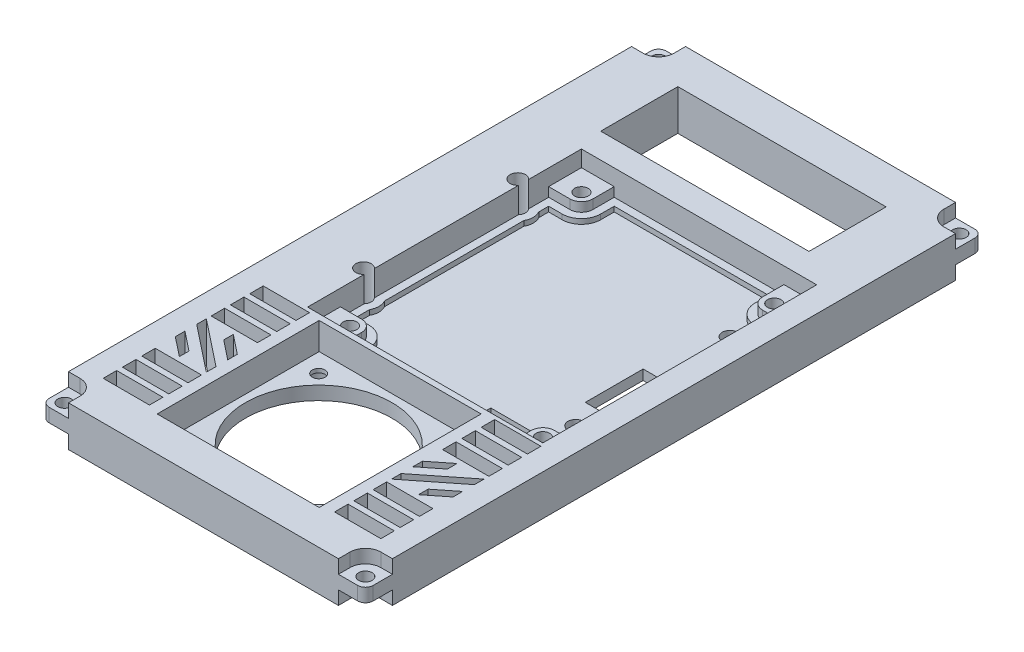
SolidWorks part; units mm, degrees
ref_plane "前视基准面" through (0, 0, 0) normal (0, 0, 1) x (1, 0, 0)
ref_plane "上视基准面" through (0, 0, 0) normal (0, 1, 0) x (1, 0, 0)
ref_plane "右视基准面" through (0, 0, 0) normal (1, 0, 0) x (0, 0, -1)
sketch "草图1" plane through (0, 0, 0) normal (0, 1, 0) x (1, 0, 0)
  line L1 (0, 0) -> (84, 0)
  line L2 (0, 0) -> (0, 160)
  line L3 (0, 160) -> (84, 160)
  line L4 (84, 0) -> (84, 160)
  dimension "D1" = 84
  dimension "D2" = 160
extrude "凸台-拉伸1" add sketch "草图1" along normal blind 10.5
fillet "圆角1" radius 2 4 edges at (0, 5.25, 0) (0, 5.25, -160) (84, 5.25, -160) (84, 5.25, 0)
sketch "草图2" plane through (0, 10.5, 0) normal (0, 1, 0) x (1, 0, 0)
  line L0 (0, 158) -> (0, 2) construction
  line L1 (2, 0) -> (82, 0) construction
  line L2 (42, 160) -> (42, 0) construction
  line L3 (82, 160) -> (2, 160) construction
  line L20 (73, 27.25) -> (78, 31.2083)
  line L21 (73, 24.75) -> (73, 27.25)
  line L22 (78, 28.7083) -> (73, 24.75)
  line L23 (78, 31.2083) -> (78, 28.7083)
  line L36 (66, 24.75) -> (66, 27.25)
  line L38 (6, 28.7083) -> (11, 24.75)
  line L40 (78, 34.25) -> (66, 24.75)
  line L42 (6, 36.75) -> (18, 36.75) construction
  line L43 (6, 36.75) -> (6, 24.75) construction
  line L44 (6, 24.75) -> (18, 24.75) construction
  line L45 (18, 36.75) -> (18, 24.75) construction
  line L46 (6, 36.75) -> (18, 24.75) construction
  line L47 (6, 24.75) -> (18, 36.75) construction
  line L48 (11, 24.75) -> (11, 27.25)
  line L49 (11, 27.25) -> (6, 31.2083)
  line L50 (6, 31.2083) -> (6, 28.7083)
  line L55 (6, 36.75) -> (6, 34.25)
  line L56 (6, 34.25) -> (18, 24.75)
  line L57 (18, 24.75) -> (18, 27.25)
  line L58 (18, 27.25) -> (6, 36.75)
  line L59 (13, 36.75) -> (13, 34.25)
  line L60 (13, 34.25) -> (18, 30.2917)
  line L61 (18, 30.2917) -> (18, 32.7917)
  line L62 (18, 32.7917) -> (13, 36.75)
  line L63 (78, 36.75) -> (78, 34.25)
  line L64 (66, 27.25) -> (78, 36.75)
  line L65 (66, 30.2917) -> (66, 32.7917)
  line L66 (71, 34.25) -> (66, 30.2917)
  line L67 (71, 36.75) -> (71, 34.25)
  line L68 (66, 32.7917) -> (71, 36.75)
  line L69 (6, 41.5) -> (6, 38)
  line L70 (6, 13.5) -> (18, 13.5)
  line L71 (6, 13.5) -> (6, 10)
  line L72 (6, 10) -> (18, 10)
  line L73 (18, 13.5) -> (18, 10)
  line L74 (6, 41.5) -> (18, 41.5)
  line L75 (18, 41.5) -> (18, 38)
  line L76 (6, 38) -> (18, 38)
  line L77 (6, 18.5) -> (6, 15)
  line L78 (6, 18.5) -> (18, 18.5)
  line L79 (18, 18.5) -> (18, 15)
  line L80 (6, 15) -> (18, 15)
  line L81 (6, 46.5) -> (6, 43)
  line L82 (6, 43) -> (18, 43)
  line L83 (18, 46.5) -> (18, 43)
  line L84 (6, 46.5) -> (18, 46.5)
  line L85 (6, 23.5) -> (6, 20)
  line L86 (6, 23.5) -> (18, 23.5)
  line L87 (18, 23.5) -> (18, 20)
  line L88 (6, 20) -> (18, 20)
  line L89 (6, 51.5) -> (6, 48)
  line L90 (6, 48) -> (18, 48)
  line L91 (18, 51.5) -> (18, 48)
  line L92 (6, 51.5) -> (18, 51.5)
  line L93 (78, 10) -> (66, 10)
  line L94 (66, 13.5) -> (66, 10)
  line L95 (78, 13.5) -> (66, 13.5)
  line L96 (78, 13.5) -> (78, 10)
  line L97 (78, 18.5) -> (66, 18.5)
  line L98 (66, 18.5) -> (66, 15)
  line L99 (78, 15) -> (66, 15)
  line L100 (78, 18.5) -> (78, 15)
  line L101 (78, 23.5) -> (66, 23.5)
  line L102 (66, 23.5) -> (66, 20)
  line L103 (78, 20) -> (66, 20)
  line L104 (78, 23.5) -> (78, 20)
  line L105 (78, 41.5) -> (66, 41.5)
  line L106 (66, 41.5) -> (66, 38)
  line L107 (78, 38) -> (66, 38)
  line L108 (78, 41.5) -> (78, 38)
  line L109 (78, 46.5) -> (66, 46.5)
  line L110 (66, 46.5) -> (66, 43)
  line L111 (78, 43) -> (66, 43)
  line L112 (78, 46.5) -> (78, 43)
  line L113 (78, 51.5) -> (66, 51.5)
  line L114 (66, 51.5) -> (66, 48)
  line L115 (78, 48) -> (66, 48)
  line L116 (78, 51.5) -> (78, 48)
  point P33 (12, 30.75)
  dimension "D1" = 6
  dimension "D4" = 24.75
  dimension "D5" = 6
  dimension "D6" = 10
  dimension "D7" = 3.5
  dimension "D8" = 12
  dimension "D9" = 2
  dimension "D10" = 3
  dimension "D25" = 12
  dimension "D26" = 12
  dimension "D27" = 2.5
  dimension "D28" = 2.5
  dimension "D29" = 2.5
  dimension "D30" = 5
  dimension "D31" = 5
extrude "切除-拉伸1" cut sketch "草图2" against normal through all
sketch "草图4" plane through (0, 10.5, 0) normal (0, 1, 0) x (1, 0, 0)
  line L0 (-0.1195, 30) -> (83.8805, 30) construction
  line L3 (41.8805, 0) -> (41.8805, 72.0189) construction
  line L5 (2, 0) -> (82, 0) construction
  line L6 (25.8805, 46) -> (57.8805, 46) construction
  line L7 (25.8805, 46) -> (25.8805, 14) construction
  line L8 (25.8805, 14) -> (57.8805, 14) construction
  line L9 (57.8805, 46) -> (57.8805, 14) construction
  circle A0 centre (41.8805, 30) radius 19
  circle A1 centre (57.8805, 14) radius 1.65
  circle A2 centre (57.8805, 46) radius 1.65
  circle A3 centre (25.8805, 46) radius 1.65
  circle A4 centre (25.8805, 14) radius 1.65
  dimension "D1" = 38
  dimension "D7" = 3.3
  dimension "D2" = 30
  dimension "D3" = 32
  dimension "D4" = 32
  dimension "D5" = 16
  dimension "D6" = 16
extrude "切除-拉伸2" cut sketch "草图4" against normal through all
sketch "草图6" plane through (0, 10.5, 0) normal (0, 1, 0) x (1, 0, 0)
  line L1 (82, 160) -> (2, 160) construction
  line L13 (66, 90) -> (76, 90)
  line L14 (66, 90) -> (66, 75)
  line L15 (66, 75) -> (76, 75)
  line L16 (76, 90) -> (76, 75)
  line L35 (55, 55) -> (67.5, 55)
  line L36 (55, 55) -> (55, 61.5)
  line L37 (55, 61.5) -> (67.5, 61.5)
  line L38 (67.5, 55) -> (67.5, 61.5)
  line L40 (84, 2) -> (84, 158) construction
  line L41 (2, 0) -> (82, 0) construction
  dimension "D2" = 70
  dimension "D3" = 8
  dimension "D4" = 16.5
  dimension "D5" = 55
  dimension "D6" = 12.5
  dimension "D7" = 6.5
  dimension "D8" = 10
  dimension "D10" = 15
extrude "切除-拉伸3" cut sketch "草图6" against normal through all
sketch "草图7" plane through (0, 10.5, 0) normal (0, 1, 0) x (1, 0, 0)
  line L0 (0, 108.5) -> (84, 108.5) construction
  line L3 (0, 68.5) -> (84, 68.5) construction
  line L4 (15, 108.5) -> (15, 68.5) construction
  line L5 (70, 108.5) -> (70, 68.5) construction
  line L7 (0, 158) -> (0, 2) construction
  line L8 (82, 160) -> (2, 160) construction
  circle A0 centre (15, 108.5) radius 2
  circle A1 centre (70, 108.5) radius 2
  circle A2 centre (15, 68.5) radius 2
  circle A3 centre (70, 68.5) radius 2
  dimension "D1" = 4
  dimension "D2" = 15
  dimension "D3" = 40
  dimension "D4" = 51.5
  dimension "D5" = 55
extrude "切除-拉伸4" cut sketch "草图7" against normal through all
sketch "草图8" plane through (0, 10.5, 0) normal (0, 1, 0) x (1, 0, 0)
  line L0 (42, 160) -> (42, 166.0083)
  line L1 (82, 160) -> (2, 160) construction
  line L4 (55, 55) -> (67.5, 55)
  line L5 (67.5, 55) -> (67.5, 61.5)
  line L6 (67.5, 61.5) -> (55, 61.5)
  line L7 (55, 61.5) -> (55, 55)
  line L25 (84, 160) -> (0, 160) construction
  line L28 (0, 160) -> (0, 0) construction
  line L31 (0, 0) -> (84, 0) construction
  line L34 (84, 0) -> (84, 160) construction
  line L176 (42, 30) -> (61, 30) construction
  line L177 (42, 30) -> (42, 11) construction
  line L179 (21, 51) -> (63, 51)
  line L180 (21, 51) -> (21, 9)
  line L181 (21, 9) -> (63, 9)
  line L182 (63, 51) -> (63, 9)
  line L189 (16.5, 123.5) -> (77.5, 123.5)
  line L190 (16.5, 123.5) -> (16.5, 52.5)
  line L191 (16.5, 52.5) -> (77.5, 52.5)
  line L192 (77.5, 123.5) -> (77.5, 52.5)
  line L194 (22, 118) -> (72, 118) construction
  line L195 (22, 118) -> (22, 58) construction
  line L196 (22, 58) -> (72, 58) construction
  line L197 (72, 118) -> (72, 58) construction
  circle A0 centre (22, 58) radius 1.75
  circle A1 centre (72, 58) radius 1.75
  circle A4 centre (72, 118) radius 1.75
  circle A5 centre (22, 118) radius 1.75
  circle A6 centre (81, 157) radius 1.75
  circle A7 centre (3, 157) radius 1.75
  circle A13 centre (22, 58) radius 3
  circle A14 centre (22, 118) radius 3
  circle A15 centre (72, 118) radius 3
  circle A16 centre (72, 58) radius 3
  circle A19 centre (81, 3) radius 1.75
  circle A20 centre (3, 3) radius 1.75
  dimension "D15" = 6
  dimension "D7" = 3.5
  dimension "D2" = 42
  dimension "D3" = 42
  dimension "D4" = 21
  dimension "D5" = 21
  dimension "D6" = 6.5
  dimension "D8" = 61
  dimension "D9" = 71
  dimension "D10" = 52.5
  dimension "D11" = 60
  dimension "D12" = 50
  dimension "D13" = 5.5
  dimension "D14" = 5.5
extrude "切除-拉伸5" cut sketch "草图8" against normal through all contours A7 | A6 | A4 | A5 | A0 | A1 | A19 | A20 region at (22, 10.5, -58) region at (72, 10.5, -58) region at (72, 10.5, -118) region at (22, 10.5, -118) region at (81, 10.5, -157) region at (3, 10.5, -157) region at (81, 10.5, -3) region at (3, 10.5, -3)
sketch "草图9" plane through (0, 10.5, 0) normal (0, 1, 0) x (1, 0, 0)
  line L8 (7, 160) -> (2, 160)
  line L9 (0, 158) -> (0, 153)
  line L10 (0, 153) -> (3, 153)
  line L11 (7, 157) -> (7, 160)
  line L16 (84, 153) -> (84, 158)
  line L17 (82, 160) -> (77, 160)
  line L18 (77, 160) -> (77, 157)
  line L19 (81, 153) -> (84, 153)
  line L24 (0, 7) -> (0, 2)
  line L25 (2, 0) -> (7, 0)
  line L26 (7, 0) -> (7, 3)
  line L27 (3, 7) -> (0, 7)
  line L32 (77, 0) -> (82, 0)
  line L33 (84, 2) -> (84, 7)
  line L34 (84, 7) -> (81, 7)
  line L35 (77, 3) -> (77, 0)
  arc A4 (2, 160) -> (0, 158) centre (2, 158) ccw
  arc A5 (3, 153) -> (7, 157) centre (3, 157) ccw
  arc A8 (84, 158) -> (82, 160) centre (82, 158) ccw
  arc A9 (77, 157) -> (81, 153) centre (81, 157) ccw
  arc A12 (0, 2) -> (2, 0) centre (2, 2) ccw
  arc A13 (7, 3) -> (3, 7) centre (3, 3) ccw
  arc A16 (82, 0) -> (84, 2) centre (82, 2) ccw
  arc A17 (81, 7) -> (77, 3) centre (81, 3) ccw
extrude "切除-拉伸6" cut sketch "草图9" against normal blind 3.5
extrude "切除-拉伸8" cut sketch "草图9<2>" along normal blind 3.5 from surface starting at face at (81, 0, -155.25)
sketch "草图9<2>" plane through (0, 10.5, 0) normal (0, 1, 0) x (1, 0, 0) same geometry as "草图9"
sketch "草图10" plane through (0, 0, 0) normal (0, -1, 0) x (-1, 0, 0)
  circle A0 centre (-71.8805, 118) radius 3.5
  circle A1 centre (-21.8805, 118) radius 3.5
  circle A2 centre (-21.8805, 58) radius 3.5
  circle A3 centre (-71.8805, 58) radius 3.5
  circle A8 centre (-57.8805, 14) radius 3
  circle A9 centre (-25.8805, 14) radius 3
  circle A10 centre (-25.8805, 46) radius 3
  circle A11 centre (-57.8805, 46) radius 3
  dimension "D1" = 7
extrude "切除-拉伸7" cut sketch "草图10" against normal blind 2.5
extrude "切除-拉伸9" cut sketch "草图8<4>" against normal blind 7 contours L182 L179 L180 L181 region at (42, 10.5, -30)
sketch "草图8<4>" plane through (0, 10.5, 0) normal (0, 1, 0) x (1, 0, 0) same geometry as "草图8"
extrude "切除-拉伸10" cut sketch "草图8<5>" against normal blind 6.5 contours L189 L192 L191 L190
sketch "草图8<5>" plane through (0, 10.5, 0) normal (0, 1, 0) x (1, 0, 0) same geometry as "草图8"
extrude "凸台-拉伸2" add sketch "草图8<6>" along normal blind 2.3 from surface contours A14 A5 | A15 A4 | A16 A1 | A13 A0 region at (19.0849, 10.5, -58) region at (19.0849, 10.5, -118) region at (69.0849, 10.5, -118) region at (69.0849, 10.5, -58) starting at face at (71, 4, -82.5)
sketch "草图8<6>" plane through (0, 10.5, 0) normal (0, 1, 0) x (1, 0, 0) same geometry as "草图8"
sketch "草图11" plane through (0, 4, 0) normal (0, 1, 0) x (1, 0, 0)
  line L0 (22, 115) -> (16.5, 115)
  line L1 (16.5, 123.5) -> (16.5, 109.8229) construction
  line L2 (16.5, 115) -> (16.5, 123.5)
  line L3 (16.5, 123.5) -> (25, 123.5)
  line L4 (16.5, 123.5) -> (77.5, 123.5) construction
  line L5 (25, 123.5) -> (25, 118)
  line L6 (72, 115) -> (77.5, 115)
  line L7 (77.5, 123.5) -> (77.5, 52.5) construction
  line L8 (77.5, 115) -> (77.5, 123.5)
  line L9 (77.5, 123.5) -> (69, 123.5)
  line L10 (16.5, 123.5) -> (77.5, 123.5) construction
  line L11 (69, 123.5) -> (69, 118)
  line L12 (72, 61) -> (77.5, 61)
  line L13 (77.5, 123.5) -> (77.5, 52.5) construction
  line L14 (77.5, 61) -> (77.5, 52.5)
  line L15 (77.5, 52.5) -> (69, 52.5)
  line L16 (16.5, 52.5) -> (77.5, 52.5) construction
  line L17 (69, 52.5) -> (69, 58)
  line L18 (22, 61) -> (16.5, 61)
  line L19 (16.5, 67.1771) -> (16.5, 52.5) construction
  line L20 (16.5, 61) -> (16.5, 52.5)
  line L21 (16.5, 52.5) -> (25, 52.5)
  line L22 (16.5, 52.5) -> (77.5, 52.5) construction
  line L23 (25, 52.5) -> (25, 58)
  circle A0 centre (22, 118) radius 3 construction
  circle A1 centre (22, 118) radius 3 construction
  circle A2 centre (72, 118) radius 3 construction
  circle A3 centre (72, 118) radius 3 construction
  circle A4 centre (72, 58) radius 3 construction
  circle A5 centre (72, 58) radius 3 construction
  circle A6 centre (22, 58) radius 3 construction
  circle A7 centre (22, 58) radius 3 construction
  circle A8 centre (22, 58) radius 3
  circle A9 centre (72, 58) radius 3
  circle A10 centre (72, 118) radius 3
  circle A11 centre (22, 118) radius 3
  circle M1 centre (72, 58) radius 3
  circle M2 centre (22, 118) radius 3
  line M12 (16.5, 67.1771) -> (16.5, 52.5)
  line M13 (16.5, 52.5) -> (77.5, 52.5)
  line M14 (77.5, 52.5) -> (77.5, 123.5)
  line M15 (77.5, 123.5) -> (16.5, 123.5)
  line M16 (16.5, 123.5) -> (16.5, 109.8229)
  circle M21 centre (72, 118) radius 3
  circle M22 centre (22, 58) radius 3
extrude "凸台-拉伸3" add sketch "草图11" along normal blind 2.3 contours L5 L0 M15 M16 M2 | L11 L6 M15 M21 M14 | L17 L12 M13 M14 M1 | L23 L18 M13 M22 M12 region at (19.7449, 4, -55.7449) region at (74.2551, 4, -55.7449) region at (74.2551, 4, -120.2551) region at (19.7449, 4, -120.2551)
sketch "草图12" plane through (0, 4, 0) normal (0, 1, 0) x (1, 0, 0)
  line L14 (25, 58) -> (25, 52.5)
  line L15 (25, 52.5) -> (69, 52.5)
  line L16 (69, 52.5) -> (69, 58)
  line L17 (72, 61) -> (77.5, 61)
  line L18 (77.5, 61) -> (77.5, 115)
  line L19 (77.5, 115) -> (72, 115)
  line L20 (69, 118) -> (69, 123.5)
  line L21 (69, 123.5) -> (25, 123.5)
  line L22 (25, 123.5) -> (25, 118)
  line L23 (22, 115) -> (16.5, 115)
  line L24 (16.5, 115) -> (16.5, 109.8229)
  line L25 (16.5, 107.1771) -> (16.5, 69.8229)
  line L26 (16.5, 67.1771) -> (16.5, 61)
  line L27 (16.5, 61) -> (22, 61)
  line L28 (25, 58) -> (25, 52.5)
  line L29 (25, 52.5) -> (69, 52.5)
  line L30 (69, 52.5) -> (69, 58)
  line L31 (72, 61) -> (77.5, 61)
  line L32 (77.5, 61) -> (77.5, 115)
  line L33 (77.5, 115) -> (72, 115)
  line L34 (69, 118) -> (69, 123.5)
  line L35 (69, 123.5) -> (25, 123.5)
  line L36 (25, 123.5) -> (25, 118)
  line L37 (22, 115) -> (16.5, 115)
  line L38 (16.5, 115) -> (16.5, 109.8229)
  line L39 (16.5, 107.1771) -> (16.5, 69.8229)
  line L40 (16.5, 67.1771) -> (16.5, 61)
  line L41 (16.5, 61) -> (22, 61)
  arc A6 (25, 58) -> (22, 61) centre (22, 58) ccw
  arc A8 (25, 58) -> (22, 61) centre (22, 58) ccw
  arc A10 (16.5, 107.1771) -> (16.5, 109.8229) centre (15, 108.5) ccw
  arc A11 (16.5, 67.1771) -> (16.5, 69.8229) centre (15, 68.5) ccw
  arc A16 (16.5, 107.1771) -> (16.5, 109.8229) centre (15, 108.5) ccw
  arc A17 (16.5, 67.1771) -> (16.5, 69.8229) centre (15, 68.5) ccw
  arc A18 (72, 61) -> (69, 58) centre (72, 58) ccw
  arc A20 (72, 61) -> (69, 58) centre (72, 58) ccw
  arc A22 (69, 118) -> (72, 115) centre (72, 118) ccw
  arc A23 (69, 118) -> (72, 115) centre (72, 118) ccw
  arc A24 (22, 115) -> (25, 118) centre (22, 118) ccw
  arc A25 (22, 115) -> (25, 118) centre (22, 118) ccw
  dimension "D1" = 0
extrude "切除-拉伸-薄壁1" cut sketch "草图12" against normal blind 0.1 thin thin type one direction reverse wall 2
sketch "草图13" plane through (0, 4, 0) normal (0, 1, 0) x (1, 0, 0)
  line L22 (72, 63) -> (75.5, 63)
  line L23 (75.5, 63) -> (75.5, 75)
  line L24 (75.5, 75) -> (66, 75)
  line L25 (66, 75) -> (66, 90)
  line L26 (66, 90) -> (75.5, 90)
  line L27 (75.5, 90) -> (75.5, 113)
  line L28 (75.5, 113) -> (72, 113)
  line L29 (67, 118) -> (67, 121.5)
  line L30 (67, 121.5) -> (27, 121.5)
  line L31 (27, 121.5) -> (27, 118)
  line L32 (22, 113) -> (18.5, 113)
  line L33 (18.5, 113) -> (18.5, 110.4365)
  line L34 (18.5, 106.5635) -> (18.5, 70.4365)
  line L35 (18.5, 66.5635) -> (18.5, 63)
  line L36 (18.5, 63) -> (22, 63)
  line L37 (27, 58) -> (27, 54.5)
  line L38 (27, 54.5) -> (67, 54.5)
  line L39 (67, 54.5) -> (67, 55)
  line L40 (67, 55) -> (55, 55)
  line L41 (55, 55) -> (55, 61.5)
  line L42 (55, 61.5) -> (67.5, 61.5)
  line L43 (67.5, 61.5) -> (67.5, 60.1794)
  line L44 (72, 63) -> (75.5, 63)
  line L45 (75.5, 63) -> (75.5, 75)
  line L46 (75.5, 75) -> (66, 75)
  line L47 (66, 75) -> (66, 90)
  line L48 (66, 90) -> (75.5, 90)
  line L49 (75.5, 90) -> (75.5, 113)
  line L50 (75.5, 113) -> (72, 113)
  line L51 (67, 118) -> (67, 121.5)
  line L52 (67, 121.5) -> (27, 121.5)
  line L53 (27, 121.5) -> (27, 118)
  line L54 (22, 113) -> (18.5, 113)
  line L55 (18.5, 113) -> (18.5, 110.4365)
  line L56 (18.5, 106.5635) -> (18.5, 70.4365)
  line L57 (18.5, 66.5635) -> (18.5, 63)
  line L58 (18.5, 63) -> (22, 63)
  line L59 (27, 58) -> (27, 54.5)
  line L60 (27, 54.5) -> (67, 54.5)
  line L61 (67, 54.5) -> (67, 55)
  line L62 (67, 55) -> (55, 55)
  line L63 (55, 55) -> (55, 61.5)
  line L64 (55, 61.5) -> (67.5, 61.5)
  line L65 (67.5, 61.5) -> (67.5, 60.1794)
  arc A6 (67, 118) -> (72, 113) centre (72, 118) ccw
  arc A8 (18.5, 106.5635) -> (18.5, 110.4365) centre (15, 108.5) ccw
  arc A9 (18.5, 66.5635) -> (18.5, 70.4365) centre (15, 68.5) ccw
  arc A10 (67, 118) -> (72, 113) centre (72, 118) ccw
  arc A14 (18.5, 106.5635) -> (18.5, 110.4365) centre (15, 108.5) ccw
  arc A15 (18.5, 66.5635) -> (18.5, 70.4365) centre (15, 68.5) ccw
  arc A18 (22, 113) -> (27, 118) centre (22, 118) ccw
  arc A20 (22, 113) -> (27, 118) centre (22, 118) ccw
  arc A22 (27, 58) -> (22, 63) centre (22, 58) ccw
  arc A23 (27, 58) -> (22, 63) centre (22, 58) ccw
  arc A24 (72, 63) -> (67.5, 60.1794) centre (72, 58) ccw
  arc A25 (72, 63) -> (67.5, 60.1794) centre (72, 58) ccw
  dimension "D1" = 0
extrude "切除-拉伸11" cut sketch "草图13" against normal blind 1.4
sketch "草图14" plane through (0, 10.5, 0) normal (0, 1, 0) x (1, 0, 0)
  line L0 (0, 153) -> (0, 7) construction
  line L1 (15, 150) -> (69, 150)
  line L2 (15, 150) -> (15, 130)
  line L3 (15, 130) -> (69, 130)
  line L4 (69, 150) -> (69, 130)
  line L5 (84, 7) -> (84, 153) construction
  line L6 (77, 160) -> (7, 160) construction
  dimension "D1" = 15
  dimension "D2" = 15
  dimension "D3" = 10
  dimension "D4" = 20
extrude "切除-拉伸12" cut sketch "草图14" against normal through all
